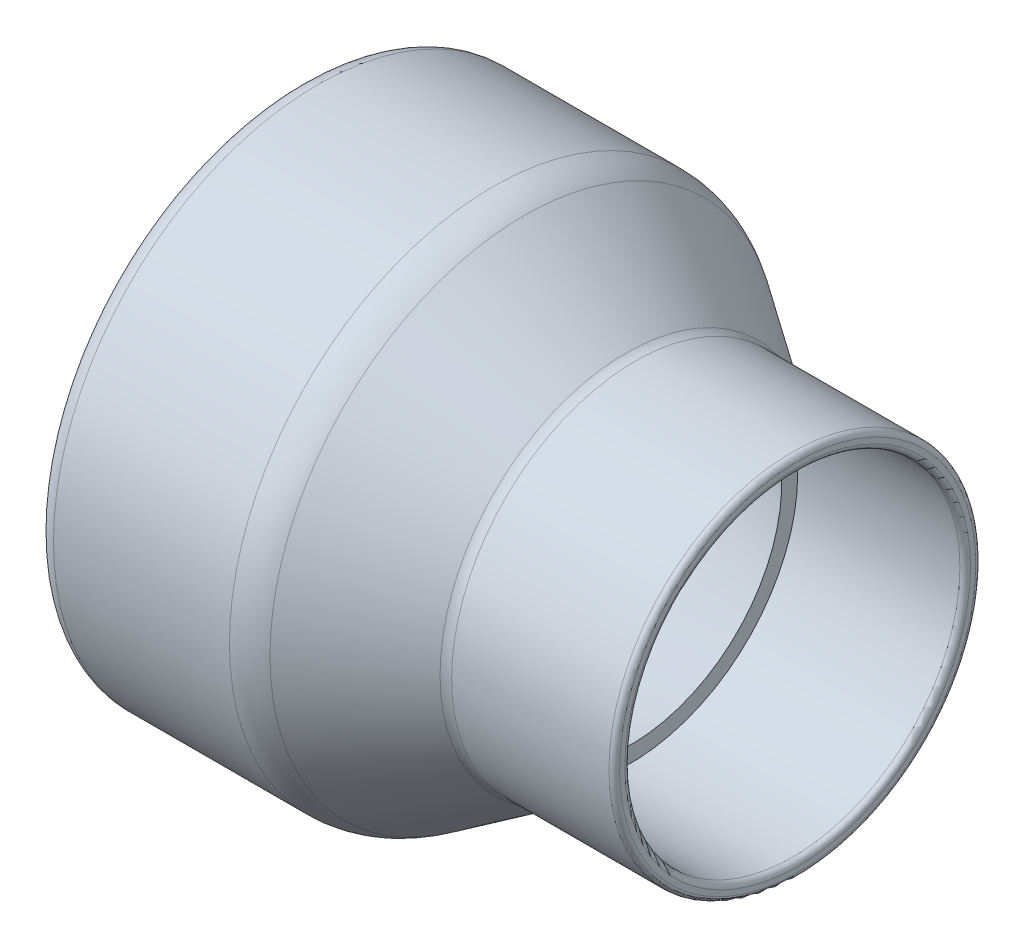
SolidWorks part; units mm, degrees
material "PE Высокой плотности"
ref_plane "Спереди" through (0, 0, 0) normal (0, 0, 1) x (1, 0, 0)
ref_plane "Сверху" through (0, 0, 0) normal (0, 1, 0) x (1, 0, 0)
ref_plane "Справа" through (0, 0, 0) normal (1, 0, 0) x (0, 0, -1)
sketch "Эскиз1" plane through (0, 0, 0) normal (0, 0, 1) x (1, 0, 0)
  line L0 (-29.76, 0) -> (29.76, 0) construction
  line L1 (-29.76, 29.3333) -> (-29.76, 27.1667)
  line L2 (-27.5933, 25) -> (-5.1933, 25)
  line L3 (-4.56, 25) -> (9.76, 20) construction
  line L4 (9.76, 20) -> (29.1267, 20)
  line L5 (29.76, 20.6333) -> (29.76, 21.2667)
  line L6 (29.1267, 21.9) -> (10.3379, 21.9)
  line L7 (9.2799, 22.2218) -> (-2.8756, 30.3708)
  line L8 (-6.5879, 31.5) -> (-27.5933, 31.5)
  line L9 (-4.56, 31.5) -> (-4.56, 29.7103) construction
  line L10 (-4.56, 23.1) -> (9.76, 18.1)
  line L11 (-4.56, 23.1) -> (-4.56, 24.3667)
  line L12 (9.76, 18.1) -> (9.76, 20)
  line L13 (9.76, 18.1) -> (20.1918, 18.1) construction
  arc A0 (-29.76, 27.1667) -> (-27.5933, 25) centre (-27.5933, 27.1667) ccw
  arc A1 (-27.5933, 31.5) -> (-29.76, 29.3333) centre (-27.5933, 29.3333) ccw
  arc A2 (29.1267, 20) -> (29.76, 20.6333) centre (29.1267, 20.6333) ccw
  arc A3 (29.76, 21.2667) -> (29.1267, 21.9) centre (29.1267, 21.2667) ccw
  arc A4 (-2.8756, 30.3708) -> (-6.5879, 31.5) centre (-6.5879, 24.8333) ccw
  arc A5 (10.3379, 21.9) -> (9.2799, 22.2218) centre (10.3379, 23.8) cw
  arc A6 (-5.1933, 25) -> (-4.56, 24.3667) centre (-5.1933, 24.3667) cw
  point P2 (-29.76, 31.5)
  point P13 (29.76, 18.1)
  point P15 (-29.76, 22.6)
  point P24 (-29.76, 31.5)
  point P29 (29.76, 21.9)
  point P36 (9.76, 21.9)
  point P40 (9.76, 0)
  point P41 (-4.56, 0)
  dimension "D4" = 59.52
  dimension "D3" = 20
  dimension "D7" = 2.1667
  dimension "D8" = 0.6333
  dimension "D9" = 6.6667
  dimension "D10" = 1.9
  dimension "D11" = 0.6333
  dimension "D5" = 25.2
  dimension "D6" = 1.9
  dimension "D1вну/2" = 31.5
  dimension "D1нар/2" = 31.5
  dimension "D2нар/2" = 25
  dimension "D2вну/2" = 22.6
  dimension "d_нар/2" = 20
  dimension "d_вну/2" = 18.1
revolve "Повернуть1" add sketch "Эскиз1" angle 360 about L0
other "Точка соединения1" parameters "Диаметр"=50, "StubLength"=0
ref_axis "Ось1" through (-14.56, 0, 0) along (1, 0, 0)
other "Точка соединения2" parameters "Диаметр"=40, "StubLength"=0
ref_axis "Ось2" through (19.76, 0, 0) along (-1, 0, 0)
other "Точка маршрута1"
equation "\"D3@Эскиз1\" = \"d_нар/2@Эскиз1\""
equation "\"D4@Эскиз1\" = 1.2 * ( \"D1вну/2@Эскиз1\" + \"d_вну/2@Эскиз1\" )"
equation "\"D5@Эскиз1\"=\"D1вну/2@Эскиз1\"*0.8"
equation "\"D6@Эскиз1\" = \"d_нар/2@Эскиз1\" - \"d_вну/2@Эскиз1\""
equation "\"D7@Эскиз1\" = ( \"D1вну/2@Эскиз1\" - \"D2нар/2@Эскиз1\" ) / 3"
equation "\"D8@Эскиз1\" = \"D6@Эскиз1\" / 3"
equation "\"D9@Эскиз1\" = \"D3@Эскиз1\" / 3"
equation "\"D10@Эскиз1\"=\"D6@Эскиз1\""
equation "\"D11@Эскиз1\"=\"D8@Эскиз1\""
